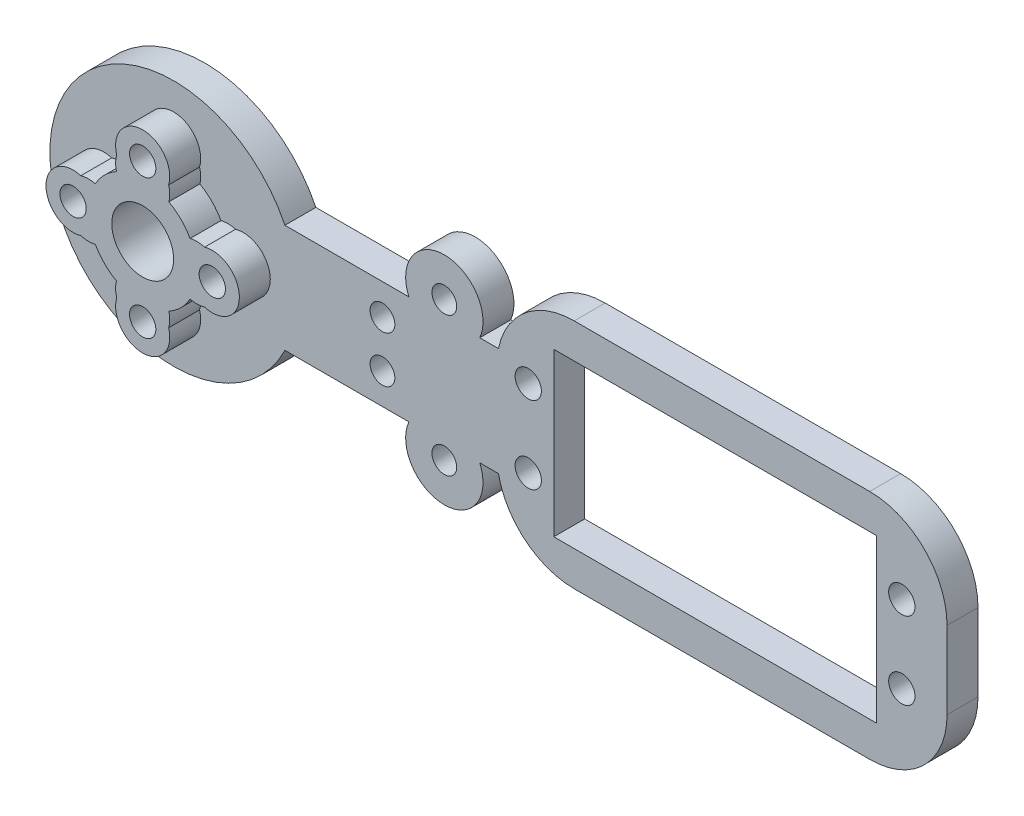
SolidWorks part; units mm, degrees
ref_plane "Front Plane" through (0, 0, 0) normal (0, 0, 1) x (1, 0, 0)
ref_plane "Top Plane" through (0, 0, 0) normal (0, 1, 0) x (1, 0, 0)
ref_plane "Right Plane" through (0, 0, 0) normal (1, 0, 0) x (0, 0, -1)
sketch "Main_web_profile" plane through (0, 0, 0) normal (0, 0, 1) x (1, 0, 0)
  line L1 (0, -7) -> (60, -7)
  line L2 (0, -7) -> (0, 7)
  line L3 (0, 7) -> (60, 7)
  line L4 (60, -7) -> (60, 7)
  dimension "D1" = 60
  dimension "D2" = 14
  dimension "D3" = 7
extrude "Main_web" add sketch "Main_web_profile" along normal blind 4
sketch "Shoulder_horn_flange_profile" plane through (0, 0, 0) normal (0, 0, 1) x (1, 0, 0)
  circle A0 centre (0, 0) radius 16
  dimension "D1" = 32
extrude "Shoulder_horn_flange" add sketch "Shoulder_horn_flange_profile" along normal blind 4
sketch "Elbow_servo_mount_profile" plane through (0, 0, 0) normal (0, 0, 1) x (1, 0, 0)
  line L1 (42, -14) -> (90, -14)
  line L2 (42, -14) -> (42, 14)
  line L3 (42, 14) -> (90, 14)
  line L4 (90, -14) -> (90, 14)
  dimension "D1" = 48
  dimension "D2" = 28
  dimension "D3" = 42
  dimension "D4" = 14
extrude "Elbow_servo_mount" add sketch "Elbow_servo_mount_profile" along normal blind 4
sketch "SG90_body_clearance_profile" plane through (0, 0, 0) normal (0, 0, 1) x (1, 0, 0)
  line L1 (53.6, -6.5) -> (77.4, -6.5)
  line L2 (53.6, -6.5) -> (53.6, 6.5)
  line L3 (53.6, 6.5) -> (77.4, 6.5)
  line L4 (77.4, -6.5) -> (77.4, 6.5)
  dimension "D1" = 23.8
  dimension "D2" = 13
  dimension "D3" = 53.6
  dimension "D4" = 6.5
extrude "SG90_body_clearance" cut sketch "SG90_body_clearance_profile" along normal through all from offset 5 offset against normal yes
sketch "Elbow_tab_fasteners_profile" plane through (0, 0, 0) normal (0, 0, 1) x (1, 0, 0)
  circle A0 centre (51, 0) radius 1.3
  circle A1 centre (80, 0) radius 1.3
  dimension "D1" = 2.6
  dimension "D2" = 2.6
  dimension "D3" = 51
  dimension "D4" = 80
extrude "Elbow_tab_fasteners" cut sketch "Elbow_tab_fasteners_profile" along normal through all from offset 50 offset against normal yes
sketch "Shoulder_center_screw_access_profile" plane through (0, 0, 0) normal (0, 0, 1) x (1, 0, 0)
  circle A0 centre (0, 0) radius 4
  dimension "D1" = 8
extrude "Shoulder_center_screw_access" cut sketch "Shoulder_center_screw_access_profile" along normal through all from offset 50 offset against normal yes
sketch "Cable_tie_holes_profile" plane through (0, 0, 0) normal (0, 0, 1) x (1, 0, 0)
  circle A0 centre (27, -3) radius 1.6
  circle A1 centre (27, 3) radius 1.6
  dimension "D1" = 3.2
  dimension "D2" = 3.2
  dimension "D3" = 27
  dimension "D4" = 3
  dimension "D5" = 3
extrude "Cable_tie_holes" cut sketch "Cable_tie_holes_profile" along normal through all from offset 50 offset against normal yes
sketch "Passive_lower_mount_boss_profile" plane through (0, 0, 0) normal (0, 0, 1) x (1, 0, 0)
  circle A0 centre (35, -9) radius 5
  dimension "D1" = 10
  dimension "D2" = 35
  dimension "D3" = 9
extrude "Passive_lower_mount_boss" add sketch "Passive_lower_mount_boss_profile" along normal blind 4
sketch "Passive_upper_mount_boss_profile" plane through (0, 0, 0) normal (0, 0, 1) x (1, 0, 0)
  circle A0 centre (35, 9) radius 5
  dimension "D1" = 10
  dimension "D2" = 35
  dimension "D3" = 9
extrude "Passive_upper_mount_boss" add sketch "Passive_upper_mount_boss_profile" along normal blind 4
sketch "Passive_cheek_standoffs_profile" plane through (0, 0, 0) normal (0, 0, 1) x (1, 0, 0)
  circle A0 centre (35, -9) radius 1.6
  circle A1 centre (35, 9) radius 1.6
  dimension "D1" = 3.2
  dimension "D2" = 3.2
  dimension "D3" = 35
  dimension "D4" = 9
  dimension "D5" = 9
extrude "Passive_cheek_standoffs" cut sketch "Passive_cheek_standoffs_profile" along normal through all from offset 50 offset against normal yes
sketch "Shoulder_dowel_support_hub_profile" plane through (0, 0, 0) normal (0, 0, 1) x (1, 0, 0)
  circle A0 centre (0, 0) radius 7
  circle A1 centre (0, 0) radius 4
  dimension "D1" = 14
  dimension "D2" = 8
extrude "Shoulder_dowel_support_hub" add sketch "Shoulder_dowel_support_hub_profile" along normal blind 4 from offset 4
sketch "Raised_M3_washer_seats_PCD14_profile" plane through (0, 0, 0) normal (0, 0, 1) x (1, 0, 0)
  circle A0 centre (7, 0) radius 3.5
  circle A1 centre (-7, 0) radius 3.5
  circle A2 centre (0, 7) radius 3.5
  circle A3 centre (0, -7) radius 3.5
  dimension "D1" = 7
  dimension "D2" = 7
  dimension "D3" = 7
  dimension "D4" = 7
  dimension "D5" = 7
  dimension "D6" = 7
  dimension "D7" = 7
  dimension "D8" = 7
extrude "Raised_M3_washer_seats_height8" add sketch "Raised_M3_washer_seats_PCD14_profile" along normal blind 4 from offset 4
sketch "Metal_horn_M3_clearance_PCD14_profile" plane through (0, 0, 0) normal (0, 0, 1) x (1, 0, 0)
  circle A0 centre (7, 0) radius 1.6
  circle A1 centre (-7, 0) radius 1.6
  circle A2 centre (0, 7) radius 1.6
  circle A3 centre (0, -7) radius 1.6
  dimension "D1" = 3.2
  dimension "D2" = 3.2
  dimension "D3" = 3.2
  dimension "D4" = 3.2
  dimension "D5" = 7
  dimension "D6" = 7
  dimension "D7" = 7
  dimension "D8" = 7
extrude "Metal_horn_M3_clearance_PCD14_SUPERSEDED_owned_servo" [suppressed] cut sketch "Metal_horn_M3_clearance_PCD14_profile" along normal through all from offset 50 offset against normal yes
sketch "Restore_shoulder_sleeve_bore_profile" plane through (0, 0, 0) normal (0, 0, 1) x (1, 0, 0)
  circle A0 centre (0, 0) radius 4
  dimension "D1" = 8
extrude "Restore_shoulder_sleeve_bore" cut sketch "Restore_shoulder_sleeve_bore_profile" along normal through all from offset 50 offset against normal yes
fillet "Fillet1" radius 7.5 4 edges at (42, -14, 2) (90, -14, 2) (90, 14, 2) (42, 14, 2)
sketch "Larger_elbow_servo_mount_replaces_SG90_opening_profile" plane through (0, 0, 0) normal (0, 0, 1) x (1, 0, 0)
  line L1 (42, -15) -> (100, -15)
  line L2 (42, -15) -> (42, 15)
  line L3 (42, 15) -> (100, 15)
  line L4 (100, -15) -> (100, 15)
  dimension "D1" = 58
  dimension "D2" = 30
  dimension "D3" = 42
  dimension "D4" = 15
extrude "Larger_elbow_servo_mount_replaces_SG90_opening" add sketch "Larger_elbow_servo_mount_replaces_SG90_opening_profile" along normal blind 4
sketch "MG996R_elbow_body_clearance_profile" plane through (0, 0, 0) normal (0, 0, 1) x (1, 0, 0)
  line L1 (49.5, -10.35) -> (91.2, -10.35)
  line L2 (49.5, -10.35) -> (49.5, 10.35)
  line L3 (49.5, 10.35) -> (91.2, 10.35)
  line L4 (91.2, -10.35) -> (91.2, 10.35)
  dimension "D1" = 41.7
  dimension "D2" = 20.7
  dimension "D3" = 49.5
  dimension "D4" = 10.35
extrude "MG996R_elbow_body_clearance_SUPERSEDED_owned_servo" [suppressed] cut sketch "MG996R_elbow_body_clearance_profile" along normal through all from offset 5 offset against normal yes
sketch "MG996R_elbow_tab_fasteners_profile" plane through (0, 0, 0) normal (0, 0, 1) x (1, 0, 0)
  circle A0 centre (47, -5) radius 1.5
  circle A1 centre (47, 5) radius 1.5
  circle A2 centre (94, -5) radius 1.5
  circle A3 centre (94, 5) radius 1.5
  dimension "D1" = 3
  dimension "D2" = 3
  dimension "D3" = 3
  dimension "D4" = 3
  dimension "D5" = 47
  dimension "D6" = 94
  dimension "D7" = 5
  dimension "D8" = 5
extrude "MG996R_elbow_tab_fasteners_SUPERSEDED_owned_servo" [suppressed] cut sketch "MG996R_elbow_tab_fasteners_profile" along normal through all from offset 50 offset against normal yes
fillet "Fillet2" radius 10 4 edges at (42, 15, 2) (42, -15, 2) (100, -15, 2) (100, 15, 2)
sketch "Owned_MG996R_elbow_body_window_profile" plane through (0, 0, 0) normal (0, 0, 1) x (1, 0, 0)
  line L1 (49.151, -10.5) -> (90.849, -10.5)
  line L2 (49.151, -10.5) -> (49.151, 10.5)
  line L3 (49.151, 10.5) -> (90.849, 10.5)
  line L4 (90.849, -10.5) -> (90.849, 10.5)
  dimension "D1" = 41.698
  dimension "D2" = 21
extrude "Owned_MG996R_elbow_body_window" cut sketch "Owned_MG996R_elbow_body_window_profile" along normal through all from offset 5 offset against normal yes
sketch "Owned_MG996R_elbow_M3_ear_holes_profile" plane through (0, 0, 0) normal (0, 0, 1) x (1, 0, 0)
  circle A0 centre (45.85, -5) radius 1.7
  circle A1 centre (45.85, 5) radius 1.7
  circle A2 centre (94.15, -5) radius 1.7
  circle A3 centre (94.15, 5) radius 1.7
  dimension "D1" = 3.4
  dimension "D2" = 3.4
  dimension "D3" = 3.4
  dimension "D4" = 3.4
extrude "Owned_MG996R_elbow_M3_ear_holes" cut sketch "Owned_MG996R_elbow_M3_ear_holes_profile" along normal through all from offset 50 offset against normal yes
sketch "Printed_hub_washer_seats_PCD18_profile" plane through (0, 0, 0) normal (0, 0, 1) x (1, 0, 0)
  circle A0 centre (9, 0) radius 3.5
  circle A1 centre (0, 9) radius 3.5
  circle A2 centre (-9, 0) radius 3.5
  circle A3 centre (0, -9) radius 3.5
  dimension "D1" = 7
  dimension "D2" = 7
  dimension "D3" = 7
  dimension "D4" = 7
extrude "Printed_hub_M3_washer_seats_PCD18" add sketch "Printed_hub_washer_seats_PCD18_profile" along normal blind 4 from offset 4
sketch "Printed_hub_M3_clearance_PCD18_profile" plane through (0, 0, 0) normal (0, 0, 1) x (1, 0, 0)
  circle A0 centre (9, 0) radius 1.7
  circle A1 centre (0, 9) radius 1.7
  circle A2 centre (-9, 0) radius 1.7
  circle A3 centre (0, -9) radius 1.7
  dimension "D1" = 3.4
  dimension "D2" = 3.4
  dimension "D3" = 3.4
  dimension "D4" = 3.4
extrude "Printed_hub_M3_clearance_PCD18" cut sketch "Printed_hub_M3_clearance_PCD18_profile" along normal through all from offset 50 offset against normal yes
